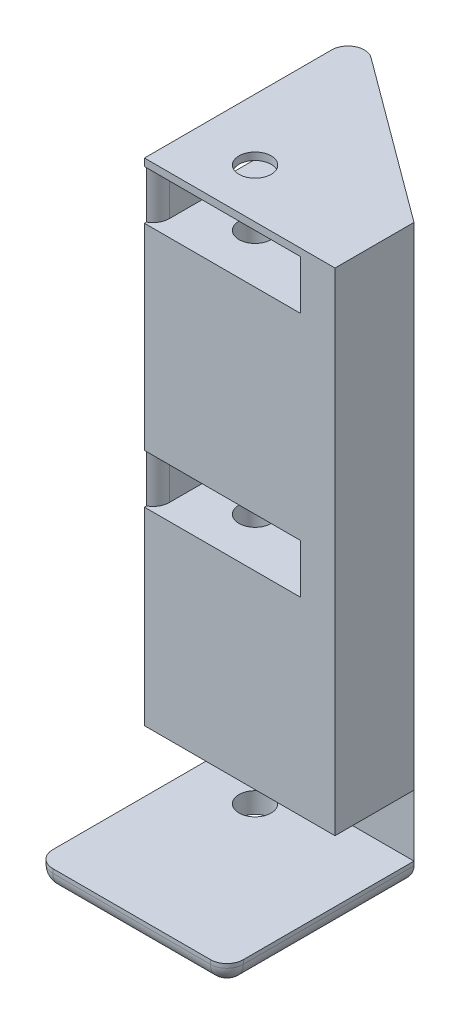
SolidWorks part; units mm, degrees
ref_plane "Front Plane" through (0, 0, 0) normal (0, 0, 1) x (1, 0, 0)
ref_plane "Top Plane" through (0, 0, 0) normal (0, 1, 0) x (1, 0, 0)
ref_plane "Right Plane" through (0, 0, 0) normal (1, 0, 0) x (0, 0, -1)
other "Bounding Box"
ref_plane "Default Plane" through (-8.9266, -12.7485, 0) normal (-0.1736, 0.9848, 0) x (0.9848, 0.1736, 0)
sketch "Sketch1" plane through (0, 0, 0) normal (0, 1, 0) x (1, 0, 0)
  line B0 (-13.2357, 21.8055) -> (-13.2357, -16.2945)
  line B1 (-13.2357, -16.2945) -> (16.2964, -16.2945)
  line B2 (16.2964, -16.2945) -> (16.2964, 0)
  line B3 (16.2964, 0) -> (-13.2357, 21.8055)
  line B4 (16.2964, 0) -> (-13.2357, 0)
sketch_block_instance "Inter mount mount-1"
sketch_block "Inter mount mount" parameters "D1"=38.1
extrude "Boss-Extrude1" add sketch "Sketch1" along normal blind 6.35 contours B4 B3 B0 | B2 B4 B0 B1 region at (-3.3916, 0, -7.2685) region at (1.5304, 0, 8.1472)
extrude "Boss-Extrude2" add sketch "Sketch1<3>" against normal blind 82.55 contours B4 B3 B0 region at (-3.3916, 0, -7.2685)
sketch "Sketch1<3>" plane through (0, 0, 0) normal (0, 1, 0) x (1, 0, 0) same geometry as "Sketch1"
sketch "Sketch2" plane through (0, 0, 0) normal (0, -1, 0) x (-1, 0, 0)
  line L0 (13.2357, 0) -> (-16.2964, 0)
  line L5 (13.2357, 0) -> (13.2357, -16.2945)
  line L6 (-16.2964, 0) -> (-16.2964, -16.2945)
  line L7 (13.2357, -16.2945) -> (-16.2964, -16.2945)
  line L8 (13.2357, -16.2945) -> (-16.2964, -16.2945) construction
extrude "Cut-Extrude1" cut sketch "Sketch2" against normal blind 3.175
sketch "Sketch4" plane through (0, 6.35, 0) normal (0, 1, 0) x (1, 0, 0)
  line L0 (16.2964, -16.2945) -> (16.2964, 0) construction
  line L1 (-13.2357, -16.2945) -> (16.2964, -16.2945)
  line L2 (-13.2357, -16.2945) -> (-13.2357, -28.9945)
  line L3 (-13.2357, -28.9945) -> (16.2964, -28.9945)
  line L4 (16.2964, -16.2945) -> (16.2964, -28.9945)
  dimension "D1" = 12.7
extrude "Boss-Extrude3" add sketch "Sketch4" against normal up to surface (3.175 mm away) up to face at (1.5304, 3.175, 8.1472)
sketch3d "3DSketch1" plane through (0, 0, 0) normal (0, 0, 1) x (1, 0, 0)
  dimension "D1" = 3.175
sketch "Sketch7" plane through (3.8639, 0, -5.2331) normal (0.594, 0, -0.8045) x (-0.8045, 0, -0.594)
  line L0 (-13.11, -82.55) -> (-13.11, 3.175) construction
  line L1 (-13.11, -73.787) -> (23.6, -73.787)
  line L2 (-13.11, -73.787) -> (-13.11, -81.407)
  line L3 (-13.11, -81.407) -> (23.6, -81.407)
  line L4 (23.6, -73.787) -> (23.6, -81.407)
  line L5 (23.6, 6.35) -> (23.6, -82.55) construction
  line L6 (-13.11, -82.55) -> (23.6, -82.55) construction
  dimension "D1" = 1.143
  dimension "D2" = 7.62
extrude "Cut-Extrude4" cut sketch "Sketch7" against normal blind 13.589 contours L2 L1 L4 L3
sketch "Sketch8" plane through (3.8639, 0, -5.2331) normal (0.594, 0, -0.8045) x (-0.8045, 0, -0.594)
  line L0 (-13.11, -82.55) -> (-13.11, 3.175) construction
  line L1 (-13.11, -43.307) -> (23.6, -43.307)
  line L2 (-13.11, -43.307) -> (-13.11, -35.687)
  line L3 (-13.11, -35.687) -> (23.6, -35.687)
  line L4 (23.6, -43.307) -> (23.6, -35.687)
  line L5 (23.6, 6.35) -> (23.6, -82.55) construction
  line L7 (-8.81, -73.787) -> (9.5942, -73.787) construction
  dimension "D1" = 30.48
  dimension "D2" = 7.62
extrude "Cut-Extrude5" cut sketch "Sketch8" against normal blind 13.589
sketch "Sketch9" plane through (0, 0, 0) normal (0, 0, 1) x (1, 0, 0)
  line L1 (-13.2357, -82.55) -> (16.2964, -82.55)
  line L2 (-13.2357, -82.55) -> (-13.2357, 3.175)
  line L3 (-13.2357, 3.175) -> (16.2964, 3.175)
  line L4 (16.2964, -82.55) -> (16.2964, 3.175)
  line L5 (-11.9261, -43.307) -> (10.9513, -43.307)
  line L6 (-11.9261, -43.307) -> (-11.9261, -35.687)
  line L7 (-11.9261, -35.687) -> (10.9513, -35.687)
  line L8 (10.9513, -43.307) -> (10.9513, -35.687)
  line L9 (-11.9261, -81.407) -> (10.9513, -81.407)
  line L10 (-11.9261, -81.407) -> (-11.9261, -73.787)
  line L11 (-11.9261, -73.787) -> (10.9513, -73.787)
  line L12 (10.9513, -81.407) -> (10.9513, -73.787)
  line L13 (-13.2357, 3.175) -> (16.2964, 3.175)
  line L14 (-13.2357, 3.175) -> (-13.2357, -6.35)
  line L15 (-13.2357, -6.35) -> (16.2964, -6.35)
  line L16 (16.2964, 3.175) -> (16.2964, -6.35)
  line M9 (10.9513, -43.307) -> (-11.9261, -43.307)
  line M10 (-11.9261, -43.307) -> (-11.9261, -35.687)
  line M11 (-11.9261, -35.687) -> (10.9513, -35.687)
  line M12 (10.9513, -35.687) -> (10.9513, -43.307)
  line M13 (10.9513, -81.407) -> (-11.9261, -81.407)
  line M14 (-11.9261, -81.407) -> (-11.9261, -73.787)
  line M15 (-11.9261, -73.787) -> (10.9513, -73.787)
  line M16 (10.9513, -73.787) -> (10.9513, -81.407)
  line M17 (16.2964, -82.55) -> (16.2964, 3.175)
  line M20 (-13.2357, -82.55) -> (16.2964, -82.55)
  dimension "D1" = 9.525
extrude "Boss-Extrude5" add sketch "Sketch9" along normal blind 12.2428 contours L15 L2 M20 M17 M16 M13 M14 M15 M12 M9 M10 M11 region at (-12.4185, -44.45, 0)
sketch "Sketch10" plane through (0, -82.55, 0) normal (0, -1, 0) x (-1, 0, 0)
  line L0 (13.2357, 21.8055) -> (13.2357, -12.2428) construction
  line L1 (13.2357, -12.2428) -> (-16.2964, -12.2428) construction
  circle A0 centre (3.7107, -4.6228) radius 2.4892
  dimension "D1" = 4.9784
  dimension "D3" = 7.62
  dimension "D2" = 9.525
extrude "Cut-Extrude6" cut sketch "Sketch10" against normal through all both and the other way through all
fillet "Fillet2" radius 2.54 7 edges at (-13.2357, -38.1, -21.8055) (-11.9261, -77.597, 0) (-11.9261, -77.597, 12.2428) (-11.9261, -39.497, 12.2428) (-11.9261, -39.497, 0) (-13.2357, 4.7625, 28.9945) (16.2964, 4.7625, 28.9945)
fillet "Fillet3" radius 2.54 7 edges at (16.2964, 6.35, 13.2272) (15.5525, 6.35, 28.2505) (1.5304, 6.35, 28.9945) (-12.4917, 6.35, 28.2505) (-13.2357, 6.35, 4.8409) (-11.8401, 6.35, -19.0403) (3.5547, 6.35, -9.408)
mirror "Mirror1" about plane through (0, 6.35, 0) normal (0, 1, 0) of bodies 114
delete or keep bodies "Body-Delete/Keep 1" type delete bodies bodies 114
